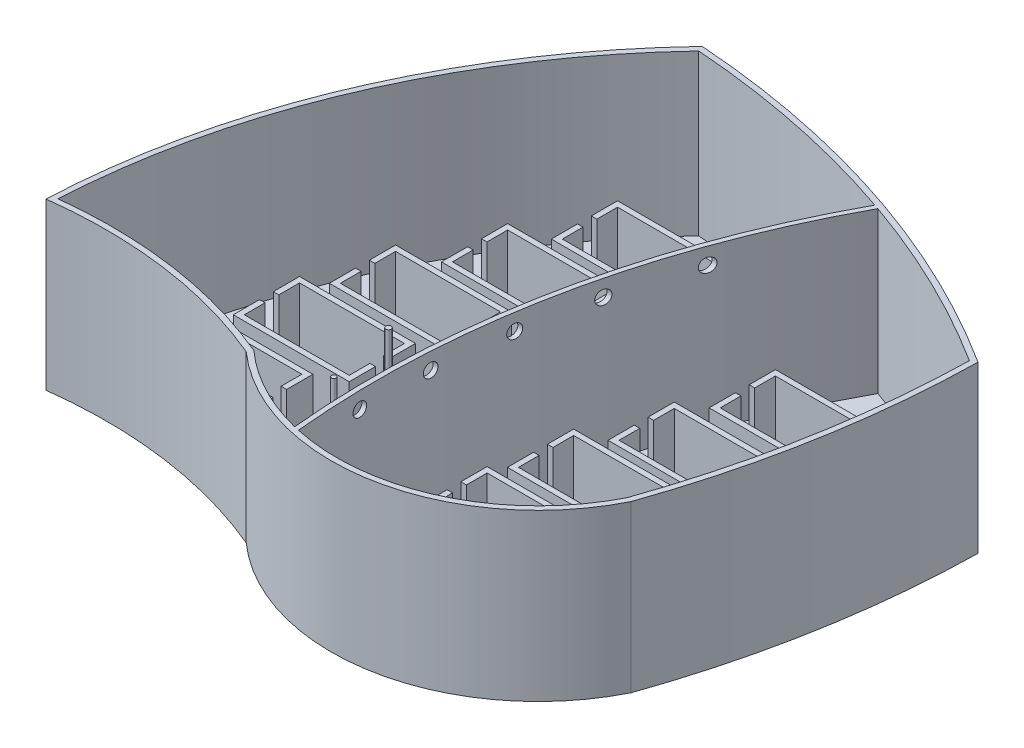
SolidWorks part; units mm, degrees
ref_plane "Front Plane" through (0, 0, 0) normal (0, 0, 1) x (1, 0, 0)
ref_plane "Top Plane" through (0, 0, 0) normal (0, 1, 0) x (1, 0, 0)
ref_plane "Right Plane" through (0, 0, 0) normal (1, 0, 0) x (0, 0, -1)
ref_plane "Plane1" through (0, 38.1, 0) normal (0, 1, 0) x (1, 0, 0)
sketch "Sketch4" plane through (0, 38.1, 0) normal (0, 1, 0) x (1, 0, 0)
  line L0 (49.8191, -114.0829) -> (-36.738, -114.0829) construction
  line L1 (-36.738, -114.0829) -> (-22.4792, -131.555) construction
  line L2 (-36.738, -114.0829) -> (-22.4792, -99.8241) construction
sketch "Sketch2" plane through (0, 0, 0) normal (0, 1, 0) x (1, 0, 0)
  line L5 (-69.85, -63.5) -> (69.85, 63.5) construction
  line L6 (-69.85, 63.5) -> (69.85, -63.5) construction
  arc A0 (69.85, 32.3186) -> (-24.7795, 63.5) centre (-38.7384, -138.0445) ccw
  arc A1 (-24.7795, 63.5) -> (-69.85, -42.38) centre (93.7433, -49.4849) ccw
  arc A2 (-69.85, -42.38) -> (-16.4221, -49.7553) centre (-56.8306, -145.2734) cw
  arc A3 (-16.4221, -49.7553) -> (57.7092, -35.3829) centre (15.1371, -14.1674) ccw
  arc A4 (57.7092, -35.3829) -> (69.85, 32.3186) centre (-146.1595, 36.1159) ccw
  point P0 (0, 0)
extrude "Boss-Extrude1" add sketch "Sketch2" along normal blind 38.1
sketch "Sketch3" plane through (0, 38.1, 0) normal (0, 1, 0) x (1, 0, 0)
  line L5 (-68.58, -62.23) -> (68.58, 62.23) construction
  line L6 (-68.58, 62.23) -> (68.58, -62.23) construction
  arc A0 (-68.5094, -40.9412) -> (-24.2714, 62.1909) centre (93.7433, -49.4849) cw
  arc A1 (-24.2714, 62.1909) -> (68.5665, 31.6292) centre (-38.7384, -138.0445) cw
  arc A2 (56.5108, -34.9626) -> (68.5665, 31.6292) centre (-146.1595, 36.1159) ccw
  arc A3 (-24.7795, 63.5) -> (-69.85, -42.38) centre (93.7433, -49.4849) ccw construction
  arc A4 (69.85, 32.3186) -> (-24.7795, 63.5) centre (-38.7384, -138.0445) ccw construction
  arc A5 (57.7092, -35.3829) -> (69.85, 32.3186) centre (-146.1595, 36.1159) ccw construction
  arc A6 (-15.7626, -48.6554) -> (56.5108, -34.9626) centre (15.1371, -14.1674) ccw
  arc A7 (-16.4221, -49.7553) -> (57.7092, -35.3829) centre (15.1371, -14.1674) ccw construction
  arc A8 (-68.5094, -40.9412) -> (-15.7626, -48.6554) centre (-56.8306, -145.2734) cw
  arc A9 (-16.4221, -49.7553) -> (-69.85, -42.38) centre (-56.8306, -145.2734) ccw construction
  point P0 (0, 0)
  point P6 (-45.5127, -25.7954)
  point P29 (-45.5127, -25.7954)
  dimension "D1" = 1.27
  dimension "D2" = 1.27
  dimension "D3" = 1.27
  dimension "D5" = 1.27
  dimension "D4" = 1.27
extrude "Cut-Extrude1" cut sketch "Sketch3" against normal blind 36.83
sketch "Sketch6" plane through (0, 0, 0) normal (0, 1, 0) x (1, 0, 0)
  line L0 (-55.0451, -31.6624) -> (-53.7751, -31.6624)
  line L5 (-64.5742, -66.5094) -> (72.5858, 57.9506) construction
  line L6 (-64.5742, 57.9506) -> (72.5858, -66.5094) construction
  line L7 (-29.6451, -36.4249) -> (-53.7751, -36.4249)
  line L8 (-29.6451, -36.4249) -> (-29.6451, -31.6624)
  line L9 (-29.6451, -23.7249) -> (-53.7751, -23.7249)
  line L10 (-53.7751, -36.4249) -> (-53.7751, -31.6624)
  line L11 (-29.6451, -36.4249) -> (-53.7751, -23.7249) construction
  line L12 (-29.6451, -23.7249) -> (-53.7751, -36.4249) construction
  line L13 (-28.3751, -37.6949) -> (-55.0451, -37.6949)
  line L14 (-28.3751, -37.6949) -> (-28.3751, -31.6624)
  line L15 (-28.3751, -22.4549) -> (-55.0451, -22.4549)
  line L16 (-55.0451, -37.6949) -> (-55.0451, -31.6624)
  line L17 (-28.3751, -37.6949) -> (-55.0451, -22.4549) construction
  line L18 (-28.3751, -22.4549) -> (-55.0451, -37.6949) construction
  line L19 (-55.0451, -28.4874) -> (-53.7751, -28.4874)
  line L20 (-55.0451, -28.4874) -> (-55.0451, -22.4549)
  line L21 (-53.7751, -28.4874) -> (-53.7751, -23.7249)
  line L22 (-29.6451, -31.6624) -> (-28.3751, -31.6624)
  line L23 (-29.6451, -28.4874) -> (-28.3751, -28.4874)
  line L24 (-29.6451, -28.4874) -> (-29.6451, -23.7249)
  line L25 (-28.3751, -28.4874) -> (-28.3751, -22.4549)
  point P0 (4.0058, -4.2794)
  point P6 (-41.7101, -30.0749)
  point P29 (-41.7101, -30.0749)
  dimension "D6" = 1.27
  dimension "D7" = 1.27
  dimension "D9" = 12.7
  dimension "D10" = 24.13
  dimension "D11" = 4.7625
  dimension "D12" = 4.7625
  dimension "D13" = 4.7625
  dimension "D14" = 4.7625
extrude "Boss-Extrude2" add sketch "Sketch6" along normal blind 13.97
sketch "Sketch7" plane through (0, 0, 0) normal (0, 1, 0) x (1, 0, 0)
  line L0 (-49.3837, -13.7318) -> (-48.1137, -13.7318)
  line L7 (-23.9837, -18.4943) -> (-48.1137, -18.4943)
  line L8 (-23.9837, -18.4943) -> (-23.9837, -13.7318)
  line L9 (-23.9837, -5.7943) -> (-48.1137, -5.7943)
  line L10 (-48.1137, -18.4943) -> (-48.1137, -13.7318)
  line L11 (-23.9837, -18.4943) -> (-48.1137, -5.7943) construction
  line L12 (-23.9837, -5.7943) -> (-48.1137, -18.4943) construction
  line L13 (-22.7137, -19.7643) -> (-49.3837, -19.7643)
  line L14 (-22.7137, -19.7643) -> (-22.7137, -13.7318)
  line L15 (-22.7137, -4.5243) -> (-49.3837, -4.5243)
  line L16 (-49.3837, -19.7643) -> (-49.3837, -13.7318)
  line L17 (-22.7137, -19.7643) -> (-49.3837, -4.5243) construction
  line L18 (-22.7137, -4.5243) -> (-49.3837, -19.7643) construction
  line L19 (-49.3837, -10.5568) -> (-48.1137, -10.5568)
  line L20 (-49.3837, -10.5568) -> (-49.3837, -4.5243)
  line L21 (-48.1137, -10.5568) -> (-48.1137, -5.7943)
  line L22 (-23.9837, -13.7318) -> (-22.7137, -13.7318)
  line L23 (-23.9837, -10.5568) -> (-22.7137, -10.5568)
  line L24 (-23.9837, -10.5568) -> (-23.9837, -5.7943)
  line L25 (-22.7137, -10.5568) -> (-22.7137, -4.5243)
  point P0 (-16.0803, -2.3763)
  point P6 (-36.0487, -12.1443)
  point P29 (-36.0487, -12.1443)
  dimension "D6" = 1.27
  dimension "D7" = 1.27
  dimension "D9" = 12.7
  dimension "D10" = 24.13
  dimension "D11" = 4.7625
  dimension "D12" = 4.7625
  dimension "D13" = 4.7625
  dimension "D14" = 4.7625
extrude "Boss-Extrude3" add sketch "Sketch7" along normal blind 13.97
sketch "Sketch15" plane through (0, 0, 0) normal (0, -1, 0) x (1, 0, 0)
  line L0 (-44.6082, -6.7708) -> (-43.3382, -6.7708)
  line L7 (-19.2082, -11.5333) -> (-43.3382, -11.5333)
  line L8 (-19.2082, -11.5333) -> (-19.2082, -6.7708)
  line L9 (-19.2082, 1.1667) -> (-43.3382, 1.1667)
  line L10 (-43.3382, -11.5333) -> (-43.3382, -6.7708)
  line L11 (-19.2082, -11.5333) -> (-43.3382, 1.1667) construction
  line L12 (-19.2082, 1.1667) -> (-43.3382, -11.5333) construction
  line L13 (-17.9382, -12.8033) -> (-44.6082, -12.8033)
  line L14 (-17.9382, -12.8033) -> (-17.9382, -6.7708)
  line L15 (-17.9382, 2.4367) -> (-44.6082, 2.4367)
  line L16 (-44.6082, -12.8033) -> (-44.6082, -6.7708)
  line L17 (-17.9382, -12.8033) -> (-44.6082, 2.4367) construction
  line L18 (-17.9382, 2.4367) -> (-44.6082, -12.8033) construction
  line L19 (-44.6082, -3.5958) -> (-43.3382, -3.5958)
  line L20 (-44.6082, -3.5958) -> (-44.6082, 2.4367)
  line L21 (-43.3382, -3.5958) -> (-43.3382, 1.1667)
  line L22 (-19.2082, -6.7708) -> (-17.9382, -6.7708)
  line L23 (-19.2082, -3.5958) -> (-17.9382, -3.5958)
  line L24 (-19.2082, -3.5958) -> (-19.2082, 1.1667)
  line L25 (-17.9382, -3.5958) -> (-17.9382, 2.4367)
  point P0 (-11.0617, 4.5847)
  point P6 (-31.2732, -5.1833)
  point P29 (-31.2732, -5.1833)
  dimension "D6" = 1.27
  dimension "D7" = 1.27
  dimension "D9" = 12.7
  dimension "D10" = 24.13
  dimension "D11" = 4.7625
  dimension "D12" = 4.7625
  dimension "D13" = 4.7625
  dimension "D14" = 4.7625
extrude "Boss-Extrude4" add sketch "Sketch15" against normal blind 13.97
sketch "Sketch16" plane through (0, 0, 0) normal (0, -1, 0) x (1, 0, 0)
  line L0 (-35.9798, -23.922) -> (-34.7098, -23.922)
  line L7 (-10.5798, -28.6845) -> (-34.7098, -28.6845)
  line L8 (-10.5798, -28.6845) -> (-10.5798, -23.922)
  line L9 (-10.5798, -15.9845) -> (-34.7098, -15.9845)
  line L10 (-34.7098, -28.6845) -> (-34.7098, -23.922)
  line L11 (-10.5798, -28.6845) -> (-34.7098, -15.9845) construction
  line L12 (-10.5798, -15.9845) -> (-34.7098, -28.6845) construction
  line L13 (-9.3098, -29.9545) -> (-35.9798, -29.9545)
  line L14 (-9.3098, -29.9545) -> (-9.3098, -23.922)
  line L15 (-9.3098, -14.7145) -> (-35.9798, -14.7145)
  line L16 (-35.9798, -29.9545) -> (-35.9798, -23.922)
  line L17 (-9.3098, -29.9545) -> (-35.9798, -14.7145) construction
  line L18 (-9.3098, -14.7145) -> (-35.9798, -29.9545) construction
  line L19 (-35.9798, -20.747) -> (-34.7098, -20.747)
  line L20 (-35.9798, -20.747) -> (-35.9798, -14.7145)
  line L21 (-34.7098, -20.747) -> (-34.7098, -15.9845)
  line L22 (-10.5798, -23.922) -> (-9.3098, -23.922)
  line L23 (-10.5798, -20.747) -> (-9.3098, -20.747)
  line L24 (-10.5798, -20.747) -> (-10.5798, -15.9845)
  line L25 (-9.3098, -20.747) -> (-9.3098, -14.7145)
  point P0 (-2.7025, -12.5665)
  point P6 (-22.6448, -22.3345)
  point P29 (-22.6448, -22.3345)
  dimension "D6" = 1.27
  dimension "D7" = 1.27
  dimension "D9" = 12.7
  dimension "D10" = 24.13
  dimension "D11" = 4.7625
  dimension "D12" = 4.7625
  dimension "D13" = 4.7625
  dimension "D14" = 4.7625
extrude "Boss-Extrude5" add sketch "Sketch16" against normal blind 13.97
sketch "Sketch17" plane through (0, 0, 0) normal (0, -1, 0) x (1, 0, 0)
  line L0 (-27.8866, -41.1082) -> (-26.6166, -41.1082)
  line L7 (-2.4866, -45.8707) -> (-26.6166, -45.8707)
  line L8 (-2.4866, -45.8707) -> (-2.4866, -41.1082)
  line L9 (-2.4866, -33.1707) -> (-26.6166, -33.1707)
  line L10 (-26.6166, -45.8707) -> (-26.6166, -41.1082)
  line L11 (-2.4866, -45.8707) -> (-26.6166, -33.1707) construction
  line L12 (-2.4866, -33.1707) -> (-26.6166, -45.8707) construction
  line L13 (-1.2166, -47.1407) -> (-27.8866, -47.1407)
  line L14 (-1.2166, -47.1407) -> (-1.2166, -41.1082)
  line L15 (-1.2166, -31.9007) -> (-27.8866, -31.9007)
  line L16 (-27.8866, -47.1407) -> (-27.8866, -41.1082)
  line L17 (-1.2166, -47.1407) -> (-27.8866, -31.9007) construction
  line L18 (-1.2166, -31.9007) -> (-27.8866, -47.1407) construction
  line L19 (-27.8866, -37.9332) -> (-26.6166, -37.9332)
  line L20 (-27.8866, -37.9332) -> (-27.8866, -31.9007)
  line L21 (-26.6166, -37.9332) -> (-26.6166, -33.1707)
  line L22 (-2.4866, -41.1082) -> (-1.2166, -41.1082)
  line L23 (-2.4866, -37.9332) -> (-1.2166, -37.9332)
  line L24 (-2.4866, -37.9332) -> (-2.4866, -33.1707)
  line L25 (-1.2166, -37.9332) -> (-1.2166, -31.9007)
  point P0 (5.4806, -29.7527)
  point P6 (-14.5516, -39.5207)
  point P29 (-14.5516, -39.5207)
  dimension "D6" = 1.27
  dimension "D7" = 1.27
  dimension "D9" = 12.7
  dimension "D10" = 24.13
  dimension "D11" = 4.7625
  dimension "D12" = 4.7625
  dimension "D13" = 4.7625
  dimension "D14" = 4.7625
extrude "Boss-Extrude6" add sketch "Sketch17" against normal blind 13.97
sketch "Sketch18" plane through (0, 0, 0) normal (0, -1, 0) x (1, 0, 0)
  line L0 (10.0641, 42.8071) -> (11.3341, 42.8071)
  line L7 (35.4641, 38.0446) -> (11.3341, 38.0446)
  line L8 (35.4641, 38.0446) -> (35.4641, 42.8071)
  line L9 (35.4641, 50.7446) -> (11.3341, 50.7446)
  line L10 (11.3341, 38.0446) -> (11.3341, 42.8071)
  line L11 (35.4641, 38.0446) -> (11.3341, 50.7446) construction
  line L12 (35.4641, 50.7446) -> (11.3341, 38.0446) construction
  line L13 (36.7341, 36.7746) -> (10.0641, 36.7746)
  line L14 (36.7341, 36.7746) -> (36.7341, 42.8071)
  line L15 (36.7341, 52.0146) -> (10.0641, 52.0146)
  line L16 (10.0641, 36.7746) -> (10.0641, 42.8071)
  line L17 (36.7341, 36.7746) -> (10.0641, 52.0146) construction
  line L18 (36.7341, 52.0146) -> (10.0641, 36.7746) construction
  line L19 (10.0641, 45.9821) -> (11.3341, 45.9821)
  line L20 (10.0641, 45.9821) -> (10.0641, 52.0146)
  line L21 (11.3341, 45.9821) -> (11.3341, 50.7446)
  line L22 (35.4641, 42.8071) -> (36.7341, 42.8071)
  line L23 (35.4641, 45.9821) -> (36.7341, 45.9821)
  line L24 (35.4641, 45.9821) -> (35.4641, 50.7446)
  line L25 (36.7341, 45.9821) -> (36.7341, 52.0146)
  point P0 (43.5107, 54.1626)
  point P6 (23.3991, 44.3946)
  point P29 (23.3991, 44.3946)
  dimension "D6" = 1.27
  dimension "D7" = 1.27
  dimension "D9" = 12.7
  dimension "D10" = 24.13
  dimension "D11" = 4.7625
  dimension "D12" = 4.7625
  dimension "D13" = 4.7625
  dimension "D14" = 4.7625
extrude "Boss-Extrude7" add sketch "Sketch18" against normal blind 13.97
sketch "Sketch19" plane through (0, 0, 0) normal (0, -1, 0) x (1, 0, 0)
  line L0 (10.0613, 26.8519) -> (11.3313, 26.8519)
  line L7 (35.4613, 22.0894) -> (11.3313, 22.0894)
  line L8 (35.4613, 22.0894) -> (35.4613, 26.8519)
  line L9 (35.4613, 34.7894) -> (11.3313, 34.7894)
  line L10 (11.3313, 22.0894) -> (11.3313, 26.8519)
  line L11 (35.4613, 22.0894) -> (11.3313, 34.7894) construction
  line L12 (35.4613, 34.7894) -> (11.3313, 22.0894) construction
  line L13 (36.7313, 20.8194) -> (10.0613, 20.8194)
  line L14 (36.7313, 20.8194) -> (36.7313, 26.8519)
  line L15 (36.7313, 36.0594) -> (10.0613, 36.0594)
  line L16 (10.0613, 20.8194) -> (10.0613, 26.8519)
  line L17 (36.7313, 20.8194) -> (10.0613, 36.0594) construction
  line L18 (36.7313, 36.0594) -> (10.0613, 20.8194) construction
  line L19 (10.0613, 30.0269) -> (11.3313, 30.0269)
  line L20 (10.0613, 30.0269) -> (10.0613, 36.0594)
  line L21 (11.3313, 30.0269) -> (11.3313, 34.7894)
  line L22 (35.4613, 26.8519) -> (36.7313, 26.8519)
  line L23 (35.4613, 30.0269) -> (36.7313, 30.0269)
  line L24 (35.4613, 30.0269) -> (35.4613, 34.7894)
  line L25 (36.7313, 30.0269) -> (36.7313, 36.0594)
  point P0 (43.3743, 38.2075)
  point P6 (23.3963, 28.4394)
  point P29 (23.3963, 28.4394)
  dimension "D6" = 1.27
  dimension "D7" = 1.27
  dimension "D9" = 12.7
  dimension "D10" = 24.13
  dimension "D11" = 4.7625
  dimension "D12" = 4.7625
  dimension "D13" = 4.7625
  dimension "D14" = 4.7625
extrude "Boss-Extrude8" add sketch "Sketch19" against normal blind 13.97
sketch "Sketch20" plane through (0, 0, 0) normal (0, -1, 0) x (1, 0, 0)
  line L0 (12.5462, 9.4253) -> (13.8162, 9.4253)
  line L7 (37.9462, 4.6628) -> (13.8162, 4.6628)
  line L8 (37.9462, 4.6628) -> (37.9462, 9.4253)
  line L9 (37.9462, 17.3628) -> (13.8162, 17.3628)
  line L10 (13.8162, 4.6628) -> (13.8162, 9.4253)
  line L11 (37.9462, 4.6628) -> (13.8162, 17.3628) construction
  line L12 (37.9462, 17.3628) -> (13.8162, 4.6628) construction
  line L13 (39.2162, 3.3928) -> (12.5462, 3.3928)
  line L14 (39.2162, 3.3928) -> (39.2162, 9.4253)
  line L15 (39.2162, 18.6328) -> (12.5462, 18.6328)
  line L16 (12.5462, 3.3928) -> (12.5462, 9.4253)
  line L17 (39.2162, 3.3928) -> (12.5462, 18.6328) construction
  line L18 (39.2162, 18.6328) -> (12.5462, 3.3928) construction
  line L19 (12.5462, 12.6003) -> (13.8162, 12.6003)
  line L20 (12.5462, 12.6003) -> (12.5462, 18.6328)
  line L21 (13.8162, 12.6003) -> (13.8162, 17.3628)
  line L22 (37.9462, 9.4253) -> (39.2162, 9.4253)
  line L23 (37.9462, 12.6003) -> (39.2162, 12.6003)
  line L24 (37.9462, 12.6003) -> (37.9462, 17.3628)
  line L25 (39.2162, 12.6003) -> (39.2162, 18.6328)
  point P0 (46.2127, 20.7808)
  point P6 (25.8812, 11.0128)
  point P29 (25.8812, 11.0128)
  dimension "D6" = 1.27
  dimension "D7" = 1.27
  dimension "D9" = 12.7
  dimension "D10" = 24.13
  dimension "D11" = 4.7625
  dimension "D12" = 4.7625
  dimension "D13" = 4.7625
  dimension "D14" = 4.7625
extrude "Boss-Extrude9" add sketch "Sketch20" against normal blind 13.97
sketch "Sketch21" plane through (0, 0, 0) normal (0, -1, 0) x (1, 0, 0)
  line L0 (18.7276, -7.5382) -> (19.9976, -7.5382)
  line L7 (44.1276, -12.3007) -> (19.9976, -12.3007)
  line L8 (44.1276, -12.3007) -> (44.1276, -7.5382)
  line L9 (44.1276, 0.3993) -> (19.9976, 0.3993)
  line L10 (19.9976, -12.3007) -> (19.9976, -7.5382)
  line L11 (44.1276, -12.3007) -> (19.9976, 0.3993) construction
  line L12 (44.1276, 0.3993) -> (19.9976, -12.3007) construction
  line L13 (45.3976, -13.5707) -> (18.7276, -13.5707)
  line L14 (45.3976, -13.5707) -> (45.3976, -7.5382)
  line L15 (45.3976, 1.6693) -> (18.7276, 1.6693)
  line L16 (18.7276, -13.5707) -> (18.7276, -7.5382)
  line L17 (45.3976, -13.5707) -> (18.7276, 1.6693) construction
  line L18 (45.3976, 1.6693) -> (18.7276, -13.5707) construction
  line L19 (18.7276, -4.3632) -> (19.9976, -4.3632)
  line L20 (18.7276, -4.3632) -> (18.7276, 1.6693)
  line L21 (19.9976, -4.3632) -> (19.9976, 0.3993)
  line L22 (44.1276, -7.5382) -> (45.3976, -7.5382)
  line L23 (44.1276, -4.3632) -> (45.3976, -4.3632)
  line L24 (44.1276, -4.3632) -> (44.1276, 0.3993)
  line L25 (45.3976, -4.3632) -> (45.3976, 1.6693)
  point P0 (52.1156, 3.8173)
  point P6 (32.0626, -5.9507)
  point P29 (32.0626, -5.9507)
  dimension "D6" = 1.27
  dimension "D7" = 1.27
  dimension "D9" = 12.7
  dimension "D10" = 24.13
  dimension "D11" = 4.7625
  dimension "D12" = 4.7625
  dimension "D13" = 4.7625
  dimension "D14" = 4.7625
extrude "Boss-Extrude10" add sketch "Sketch21" against normal blind 13.97
sketch "Sketch22" plane through (0, 0, 0) normal (0, -1, 0) x (1, 0, 0)
  line L0 (23.9014, -25.6326) -> (25.1714, -25.6326)
  line L7 (49.3014, -30.3951) -> (25.1714, -30.3951)
  line L8 (49.3014, -30.3951) -> (49.3014, -25.6326)
  line L9 (49.3014, -17.6951) -> (25.1714, -17.6951)
  line L10 (25.1714, -30.3951) -> (25.1714, -25.6326)
  line L11 (49.3014, -30.3951) -> (25.1714, -17.6951) construction
  line L12 (49.3014, -17.6951) -> (25.1714, -30.3951) construction
  line L13 (50.5714, -31.6651) -> (23.9014, -31.6651)
  line L14 (50.5714, -31.6651) -> (50.5714, -25.6326)
  line L15 (50.5714, -16.4251) -> (23.9014, -16.4251)
  line L16 (23.9014, -31.6651) -> (23.9014, -25.6326)
  line L17 (50.5714, -31.6651) -> (23.9014, -16.4251) construction
  line L18 (50.5714, -16.4251) -> (23.9014, -31.6651) construction
  line L19 (23.9014, -22.4576) -> (25.1714, -22.4576)
  line L20 (23.9014, -22.4576) -> (23.9014, -16.4251)
  line L21 (25.1714, -22.4576) -> (25.1714, -17.6951)
  line L22 (49.3014, -25.6326) -> (50.5714, -25.6326)
  line L23 (49.3014, -22.4576) -> (50.5714, -22.4576)
  line L24 (49.3014, -22.4576) -> (49.3014, -17.6951)
  line L25 (50.5714, -22.4576) -> (50.5714, -16.4251)
  point P0 (57.6091, -14.277)
  point P6 (37.2364, -24.0451)
  point P29 (37.2364, -24.0451)
  dimension "D6" = 1.27
  dimension "D7" = 1.27
  dimension "D9" = 12.7
  dimension "D10" = 24.13
  dimension "D11" = 4.7625
  dimension "D12" = 4.7625
  dimension "D13" = 4.7625
  dimension "D14" = 4.7625
extrude "Boss-Extrude11" add sketch "Sketch22" against normal blind 13.97
sketch "Sketch23" plane through (0, 38.1, 0) normal (0, 1, 0) x (1, 0, 0)
  arc A0 (5.2406, -59.4032) -> (27.7432, 51.3854) centre (196.3221, -40.5347) cw
  arc A1 (-15.7626, -48.6554) -> (56.5108, -34.9626) centre (15.1371, -14.1674) ccw construction
  arc A2 (68.5665, 31.6292) -> (-24.2714, 62.1909) centre (-38.7384, -138.0445) ccw construction
  arc A3 (4.1166, -59.1426) -> (26.6965, 51.7495) centre (196.3221, -40.5347) cw
  arc A4 (-15.7626, -48.6554) -> (56.5108, -34.9626) centre (15.1371, -14.1674) ccw construction
  arc A5 (68.5665, 31.6292) -> (-24.2714, 62.1909) centre (-38.7384, -138.0445) ccw construction
  arc A6 (26.6965, 51.7495) -> (27.7432, 51.3854) centre (26.141, 48.4661) cw
  arc A7 (4.1166, -59.1426) -> (5.2406, -59.4032) centre (5.121, -57.3649) ccw
  circle A8 centre (-1.3469, -44.6647) radius 0.5289
  circle A9 centre (-4.8256, -28.6102) radius 0.6158
  point P23 (0, 0)
  point P24 (0, 0)
extrude "Divider for Back Rank tendons" add sketch "Sketch23" against normal blind 36.83
sketch "Sketch24" plane through (0, 0, 0) normal (1, 0, 0) x (0, 0, -1)
  line L0 (-35.3829, 38.1) -> (-61.7329, 38.1) construction
  line L1 (32.3186, 38.1) -> (-35.3829, 38.1) construction
  line L2 (-45.9821, 13.97) -> (-45.9821, 1.27) construction
  line L3 (-30.0269, 13.97) -> (-30.0269, 1.27) construction
  line L4 (-12.6003, 13.97) -> (-12.6003, 1.27) construction
  line L5 (4.3632, 13.97) -> (4.3632, 1.27) construction
  line L6 (22.4576, 13.97) -> (22.4576, 1.27) construction
  circle A0 centre (-44.3946, 34.29) radius 1.5875
  circle A1 centre (-28.4394, 34.29) radius 1.5875
  circle A2 centre (-11.0128, 34.29) radius 1.5875
  circle A3 centre (5.9507, 34.29) radius 1.5875
  circle A4 centre (24.3571, 34.29) radius 1.5875
  point P4 (0, 0)
  point P5 (0, 0)
  point P14 (0, 0)
  point P17 (0, 0)
  point P18 (0, 0)
  point P19 (0, 0)
  dimension "D6" = 1.5875
  dimension "D7" = 1.5875
  dimension "D1" = 3.81
  dimension "D2" = 3.81
  dimension "D3" = 3.81
  dimension "D4" = 3.81
  dimension "D5" = 3.81
  dimension "D8" = 1.5875
  dimension "D9" = 1.5875
  dimension "D10" = 1.8995
extrude "Back Rank HOles" cut sketch "Sketch24" along normal blind 25.4
